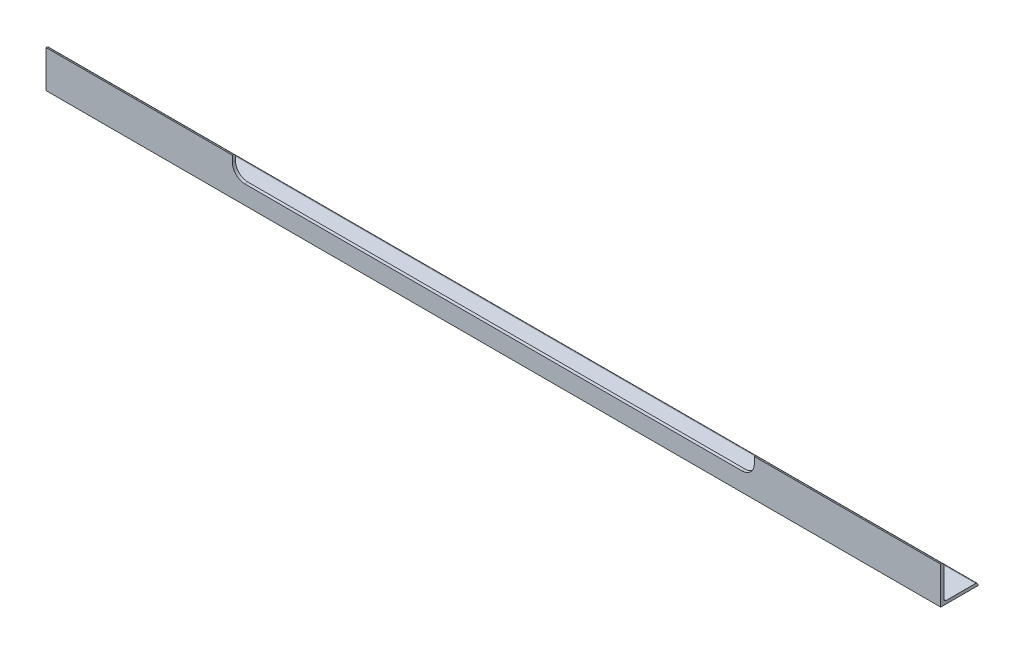
SolidWorks part; units mm, degrees
material "6063-T6"
ref_plane "Front Plane" through (0, 0, 0) normal (0, 0, 1) x (1, 0, 0)
ref_plane "Top Plane" through (0, 0, 0) normal (0, 1, 0) x (1, 0, 0)
ref_plane "Right Plane" through (0, 0, 0) normal (1, 0, 0) x (0, 0, -1)
sketch "Sketch1" plane through (0, 0, 0) normal (1, 0, 0) x (0, 0, -1)
  line L0 (0, 76.2) -> (0, 0)
  line L1 (0, 0) -> (76.2, 0)
  line L2 (6.35, 71.12) -> (6.35, 11.43)
  line L3 (11.43, 6.35) -> (71.12, 6.35)
  line L4 (0, 76.2) -> (1.27, 76.2)
  line L5 (76.2, 1.27) -> (76.2, 0)
  line L6 (6.35, 76.2) -> (6.35, 6.35) construction
  line L7 (6.35, 6.35) -> (76.2, 6.35) construction
  arc A0 (6.35, 11.43) -> (11.43, 6.35) centre (11.43, 11.43) ccw
  arc A1 (71.12, 6.35) -> (76.2, 1.27) centre (71.12, 1.27) cw
  arc A2 (6.35, 71.12) -> (1.27, 76.2) centre (1.27, 71.12) ccw
  dimension "D1" = 76.2
  dimension "D3" = 5.08
  dimension "D2" = 6.35
extrude "Boss-Extrude1" add sketch "Sketch1" along normal blind 914.4 and the other way blind 914.4
sketch "Sketch2" plane through (0, 0, 0) normal (0, 0, 1) x (1, 0, 0)
  line L0 (-914.4, 76.2) -> (914.4, 76.2) construction
  line L1 (-533.4, 76.2) -> (533.4, 76.2)
  line L2 (-533.4, 76.2) -> (-533.4, 38.1)
  line L3 (-533.4, 38.1) -> (533.4, 38.1)
  line L4 (533.4, 76.2) -> (533.4, 38.1)
  line L5 (-914.4, 76.2) -> (-914.4, 0) construction
  line L6 (-914.4, 0) -> (914.4, 0) construction
  point P8 (-914.4, 38.1)
  dimension "D1" = 381
  dimension "D2" = 1447.8
  dimension "D3" = 38.1
extrude "Cut-Extrude1" cut sketch "Sketch2" against normal through all
fillet "Fillet1" radius 25.4 2 edges at (533.4, 38.1, -3.175) (-533.4, 38.1, -3.175)
